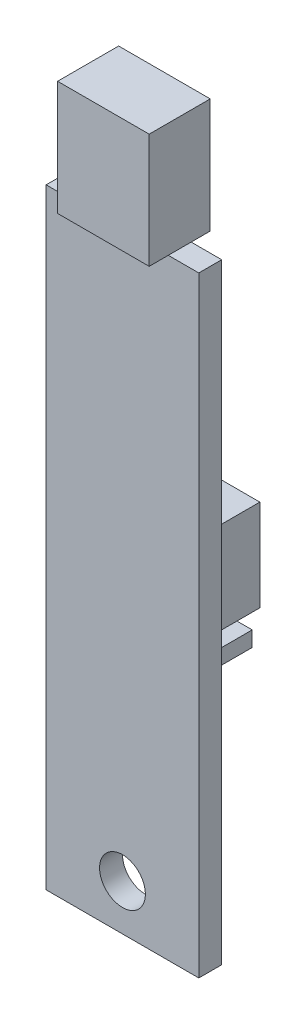
SolidWorks part; units mm, degrees
ref_plane "前基準面" through (0, 0, 0) normal (0, 0, 1) x (1, 0, 0)
ref_plane "上基準面" through (0, 0, 0) normal (0, 1, 0) x (1, 0, 0)
ref_plane "右基準面" through (0, 0, 0) normal (1, 0, 0) x (0, 0, -1)
sketch "草圖2" plane through (0, 0, 0) normal (0, 0, 1) x (1, 0, 0)
  line L1 (0, 0) -> (10, 0)
  line L2 (0, 0) -> (0, 40)
  line L3 (0, 40) -> (10, 40)
  line L4 (10, 0) -> (10, 40)
  circle A0 centre (5, 3) radius 1.5
  dimension "D4" = 3
  dimension "D1" = 40
  dimension "D2" = 10
  dimension "D3" = 3
extrude "填料-伸長1" add sketch "草圖2" along normal blind 1.5
sketch "草圖3" plane through (0, 0, 1.5) normal (0, 0, 1) x (1, 0, 0)
  line L0 (10, 0) -> (10, 40) construction
  line L1 (0, 40) -> (10, 40)
  line L2 (0, 40) -> (0, 20)
  line L3 (0, 20) -> (10, 20)
  line L4 (10, 40) -> (10, 20)
  line L5 (2, 14) -> (8, 14)
  line L6 (0, 40) -> (10, 40)
  line L7 (0, 40) -> (0, 30)
  line L8 (0, 30) -> (10, 30)
  line L9 (10, 40) -> (10, 30)
  line L10 (0, 40) -> (10, 40)
  line L11 (0, 40) -> (0, 15)
  line L12 (0, 15) -> (10, 15)
  line L13 (10, 40) -> (10, 15)
  line L14 (8, 23) -> (2, 23)
  line L15 (8, 23) -> (8, 17)
  line L16 (8, 17) -> (2, 17)
  line L17 (2, 23) -> (2, 17)
  line L18 (2, 15) -> (8, 15)
  line L19 (2, 14) -> (2, 16)
  line L20 (2, 16) -> (8, 16)
  line L21 (8, 14) -> (8, 16)
  line L22 (2, 32) -> (8, 32)
  line L23 (2, 30) -> (8, 30)
  line L24 (2, 32) -> (2, 28)
  line L25 (2, 28) -> (8, 28)
  line L26 (8, 32) -> (8, 28)
  circle A0 centre (5, 20) radius 3
  dimension "D4" = 1
  dimension "D1" = 20
  dimension "D2" = 10
  dimension "D3" = 25
  dimension "D5" = 2
extrude "填料-伸長2" [suppressed] add sketch "草圖3" along normal blind 8 contours L22 L26 L25 L24
extrude "填料-伸長3" add sketch "草圖3<3>" against normal blind 6 contours L14 L17 L16 L15
sketch "草圖3<3>" plane through (0, 0, 1.5) normal (0, 0, 1) x (1, 0, 0) same geometry as "草圖3"
extrude "填料-伸長4" add sketch "草圖3<4>" against normal blind 2 contours L21 L20 L19 L5
sketch "草圖3<4>" plane through (0, 0, 1.5) normal (0, 0, 1) x (1, 0, 0) same geometry as "草圖3"
sketch "草圖4" plane through (0, 0, -0.5) normal (0, 0, -1) x (-1, 0, 0)
  line L0 (-2, 14) -> (-8, 14) construction
  line L1 (-8, 16) -> (-6, 16)
  line L2 (-8, 16) -> (-8, 14)
  line L3 (-8, 14) -> (-6, 14)
  line L4 (-6, 16) -> (-6, 14)
  line L5 (-4, 16) -> (-4, 14)
  line L6 (-6, 16) -> (-4, 16)
  line L7 (-6, 16) -> (-6, 14)
  line L8 (-6, 14) -> (-4, 14)
  line L9 (-2, 16) -> (-2, 14)
  line L10 (-4, 16) -> (-2, 16)
  line L11 (-4, 16) -> (-4, 14)
  line L12 (-4, 14) -> (-2, 14)
  line L13 (-4.5, 15.5) -> (-5.5, 15.5)
  line L14 (-5.5, 15.5) -> (-5.5, 14.5)
  line L15 (-4.5, 14.5) -> (-5.5, 14.5)
  line L16 (-6.5, 15.5) -> (-7.5, 15.5)
  line L17 (-6.5, 15.5) -> (-6.5, 14.5)
  line L18 (-6.5, 14.5) -> (-7.5, 14.5)
  line L19 (-7.5, 15.5) -> (-7.5, 14.5)
  line L20 (-4.5, 15.5) -> (-4.5, 14.5)
  line L21 (-2.5, 15.5) -> (-3.5, 15.5)
  line L22 (-3.5, 15.5) -> (-3.5, 14.5)
  line L23 (-2.5, 14.5) -> (-3.5, 14.5)
  line L24 (-2.5, 15.5) -> (-2.5, 14.5)
  dimension "D3" = 3
  dimension "D1" = 2
  dimension "D2" = 3
extrude "填料-伸長5" add sketch "草圖4" along normal blind 4 contours L16 L19 L18 L17 | L20 L13 L14 L15 | L24 L21 L22 L23 region at (5, 15, -0.5) region at (7, 15, -0.5) region at (3, 15, -0.5)
sketch "草圖5" [suppressed] plane through (0, 0, 9.5) normal (0, 0, 1) x (1, 0, 0)
  line L1 (8, 32) -> (2, 32)
  line L2 (8, 32) -> (8, 28)
  line L3 (8, 28) -> (2, 28)
  line L4 (2, 32) -> (2, 28)
  circle A0 centre (3.5, 30) radius 1
  circle A1 centre (6.5, 30) radius 1
  dimension "D3" = 2
  dimension "D4" = 2
  dimension "D1" = 1.5
  dimension "D2" = 1.5
extrude "除料-伸長1" [suppressed] cut sketch "草圖5" against normal blind 0.5
sketch "草圖6" plane through (0, 40, 0) normal (0, 1, 0) x (1, 0, 0)
  line L1 (2, 1.25) -> (8, 1.25)
  line L2 (2, 1.25) -> (2, -2.75)
  line L3 (2, -2.75) -> (8, -2.75)
  line L4 (8, 1.25) -> (8, -2.75)
  line L6 (0, -0.75) -> (10.0907, -0.75) construction
  line L7 (0, -1.5) -> (0, 0) construction
  dimension "D1" = 4
  dimension "D2" = 6
  dimension "D3" = 6
extrude "填料-伸長6" add sketch "草圖6" along normal blind 7.5
